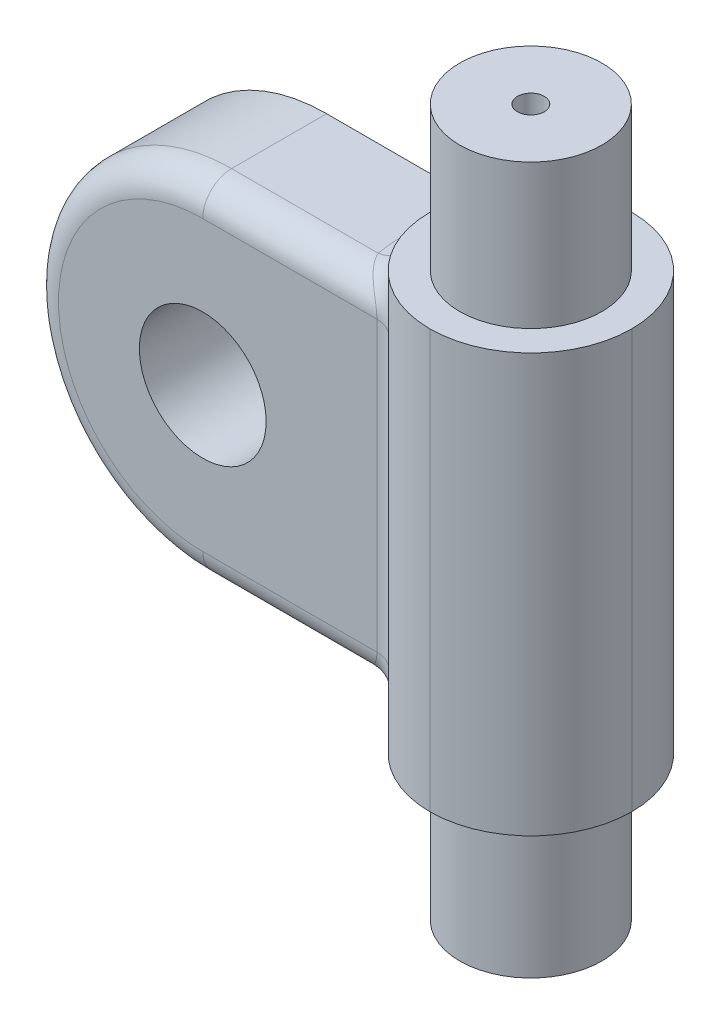
SolidWorks part; units mm, degrees
ref_plane "Front Plane" through (0, 0, 0) normal (0, 0, 1) x (1, 0, 0)
ref_plane "Top Plane" through (0, 0, 0) normal (0, 1, 0) x (1, 0, 0)
ref_plane "Right Plane" through (0, 0, 0) normal (1, 0, 0) x (0, 0, -1)
sketch "Sketch3" plane through (0, 0, 0) normal (0, 0, 1) x (1, 0, 0)
  line L0 (0, 15.24) -> (15.24, 15.24) construction
  line L1 (15.24, 31.115) -> (33.02, 31.115)
  line L2 (15.24, 31.115) -> (15.24, 15.24)
  line L3 (15.24, -31.115) -> (33.02, -31.115)
  line L4 (33.02, 31.115) -> (33.02, -31.115)
  line L5 (0, -15.24) -> (15.24, -15.24) construction
  line L6 (15.24, -15.24) -> (15.24, -31.115)
  line L7 (15.24, -15.24) -> (15.24, 15.24)
  arc A0 (0, 15.24) -> (0, -15.24) centre (0, 0) ccw construction
  dimension "D1" = 30.48
  dimension "D2" = 15.24
  dimension "D3" = 31.115
  dimension "D4" = 31.115
  dimension "D5" = 17.78
extrude "Boss-Extrude1" add sketch "Sketch3" along normal blind 8.89 and the other way blind 8.89
ref_plane "Plane1" through (0, 0, 0) normal (0, 0, 1) x (1, 0, 0)
sketch "Sketch4" plane through (0, 0, 0) normal (0, 0, 1) x (1, 0, 0)
  line L0 (0, 15.24) -> (15.24, 15.24)
  line L1 (15.24, 31.115) -> (33.02, 31.115) construction
  line L2 (15.24, 31.115) -> (15.24, 15.24) construction
  line L3 (15.24, -31.115) -> (33.02, -31.115) construction
  line L4 (33.02, 31.115) -> (33.02, -31.115) construction
  line L5 (0, -15.24) -> (15.24, -15.24)
  line L6 (15.24, -15.24) -> (15.24, -31.115) construction
  line L7 (15.24, 15.24) -> (15.24, -15.24)
  arc A0 (0, 15.24) -> (0, -15.24) centre (0, 0) ccw
  dimension "D1" = 30.48
  dimension "D2" = 15.24
  dimension "D3" = 31.115
  dimension "D4" = 31.115
  dimension "D5" = 17.78
extrude "Boss-Extrude2" add sketch "Sketch4" along normal blind 4.7625 and the other way blind 4.7625
sketch "Sketch5" plane through (0, 0, -4.7625) normal (0, 0, -1) x (-1, 0, 0)
  line L0 (0, -15.24) -> (-15.24, -15.24)
  line L1 (-15.24, -15.24) -> (-15.24, 15.24)
  line L2 (-15.24, 15.24) -> (0, 15.24)
  arc A0 (0, -15.24) -> (0, 15.24) centre (0, 0) ccw
  circle A1 centre (0, 0) radius 7.2708
  dimension "D1" = 14.5415
extrude "Boss-Extrude3" add sketch "Sketch5" along normal blind 1.3843
sketch "Sketch6" plane through (0, 0, 4.7625) normal (0, 0, 1) x (1, 0, 0)
  circle A0 centre (0, 0) radius 5.5816
  dimension "D1" = 11.1633
extrude "Cut-Extrude2" cut sketch "Sketch6" against normal through all
sketch "Sketch7" plane through (0, 31.115, 0) normal (0, 1, 0) x (1, 0, 0)
  line L0 (24.13, -8.89) -> (24.13, 8.89) construction
  line L1 (33.02, -8.89) -> (15.24, -8.89) construction
  line L2 (33.02, 8.89) -> (15.24, 8.89) construction
  line L4 (33.02, -8.89) -> (15.24, -8.89)
  line L5 (33.02, -8.89) -> (33.02, 8.89)
  line L6 (33.02, 8.89) -> (15.24, 8.89)
  line L7 (15.24, -8.89) -> (15.24, 8.89)
  circle A0 centre (24.13, 0) radius 6.2611
  dimension "D1" = 12.5222
extrude "Cut-Extrude3" cut sketch "Sketch7" against normal blind 12.7
mirror "Mirror1" about plane through (0, 0, 0) normal (0, 1, 0) of "Cut-Extrude3"
fillet "Fillet2" radius 8.89 4 edges at (33.02, 0, -8.89) (33.02, 0, 8.89) (15.24, 0, -8.89) (15.24, 0, 8.89)
fillet "Fillet4" radius 2.54 9 edges at (15.5928, -15.24, 2.4797) (15.8799, 15.24, -3.3118) (8.3116, -15.24, 4.7625) (-15.24, 0, 4.7625) (15.8799, -15.24, -3.3118) (17.7075, 0, -6.1468) (15.5928, 15.24, 2.4797) (8.3116, 15.24, 4.7625) (16.6233, 0, 4.7625)
sketch "Sketch9" plane through (0, 31.115, 0) normal (0, 1, 0) x (1, 0, 0)
  circle A0 centre (24.13, 0) radius 1.1811
  circle A1 centre (24.13, 0) radius 6.2611 construction
extrude "Cut-Extrude4" cut sketch "Sketch9" against normal through all
equation "\"DiffLinkID\"= .5in"
equation "\"DiffLinkTHK\"= .1in"
equation "\"SupportLinkID\"= 1in"
equation "\"D1@Sketch3\"=\"SupportLinkID\"+2*(\"DiffLinkTHK\")"
equation "\"D2@Sketch3\"=\"D1@Sketch3\"/2"
equation "\"D3@Sketch3\"=\"D1@Sketch3\"/2+(\"DiffLinkID\")+.125"
equation "\"D4@Sketch3\"=\"D3@Sketch3\""
equation "\"D5@Sketch3\"=\"DiffLinkID\"+2*(\"DiffLinkTHK\")"
equation "\"D1@Boss-Extrude1\"=(\"DiffLinkID\"+2*(\"DiffLinkTHK\"))/2"
equation "\"D2@Boss-Extrude1\"=(\"DiffLinkID\"+2*(\"DiffLinkTHK\"))/2"
equation "\"D1@Boss-Extrude2\"=3/16"
equation "\"D2@Boss-Extrude2\"=3/16"
equation "\"D1@Sketch5\"=9/16+.01"
equation "\"D1@Sketch6\"=7/16+.002"
equation "\"D1@Sketch7\"=.5-.007"
equation "\"D1@Fillet2\"=(\"DiffLinkID\"+2*(\"DiffLinkTHK\"))/2"
equation "\"D1@Sketch9\"=\"DiffLinkTHK\"*2"
